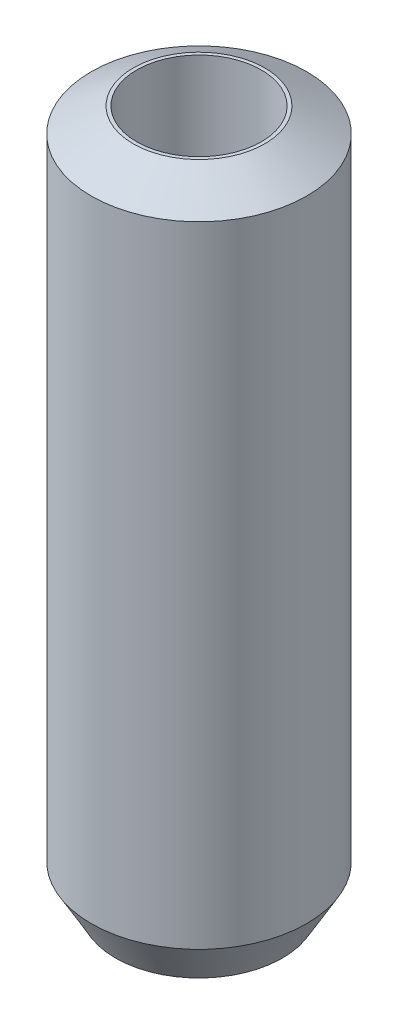
SolidWorks part; units mm, degrees
ref_plane "Front Plane" through (0, 0, 0) normal (0, 0, 1) x (1, 0, 0)
ref_plane "Top Plane" through (0, 0, 0) normal (0, 1, 0) x (1, 0, 0)
ref_plane "Right Plane" through (0, 0, 0) normal (1, 0, 0) x (0, 0, -1)
sketch "Sketch1" plane through (0, 0, 0) normal (0, 1, 0) x (1, 0, 0)
  circle A0 centre (0, 0) radius 12.5
  dimension "SHAFT_OD" = 25
extrude "Boss-Extrude1" add sketch "Sketch1" along normal blind 80.7942
sketch "Sketch2" plane through (0, 0, 0) normal (0, 1, 0) x (1, 0, 0)
  circle A0 centre (0, 0) radius 7.2306
  dimension "BORE_D" = 14.4611
extrude "Cut-Extrude1" cut sketch "Sketch2" along normal through all
chamfer "Chamfer1" distance 2.8114 angle 60 2 edges at (0, 80.7942, 12.5) (0, 0, 12.5) first distance on face at (0, 80.7942, 12.5) first distance on face at (0, 0, 7.2306)
